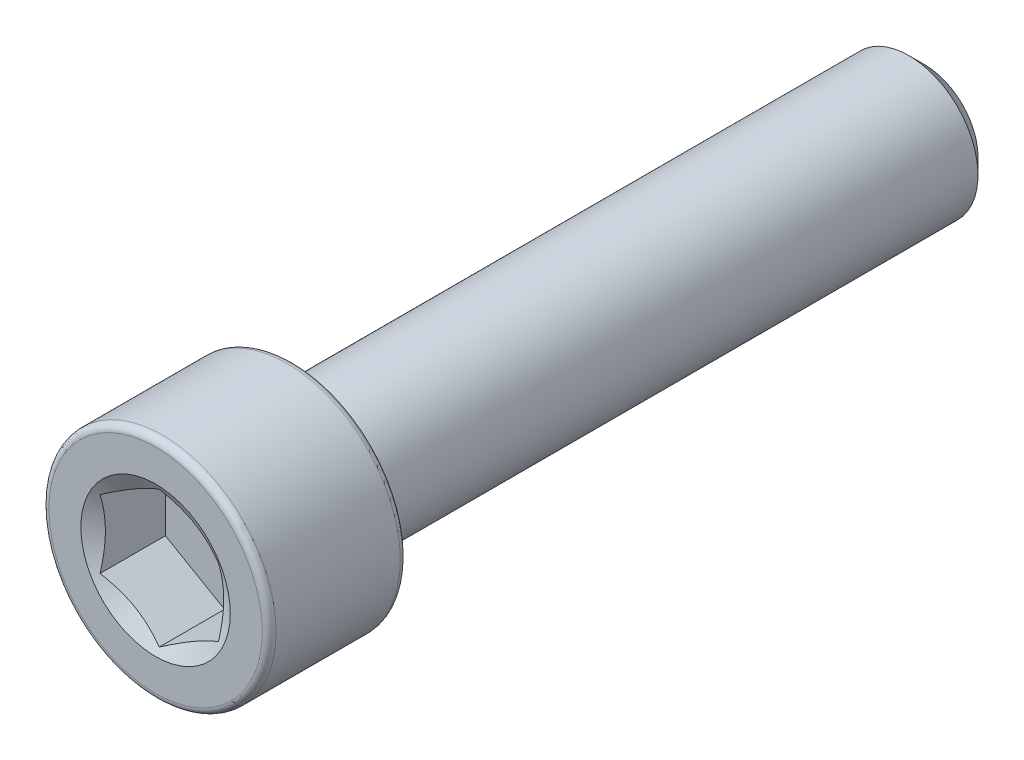
SolidWorks part; units mm, degrees
material "Alloy Steel (SS)"
ref_plane "Front Plane" through (0, 0, 0) normal (0, 0, 1) x (1, 0, 0)
ref_plane "Top Plane" through (0, 0, 0) normal (0, 1, 0) x (1, 0, 0)
ref_plane "Right Plane" through (0, 0, 0) normal (1, 0, 0) x (0, 0, -1)
sketch "Sketch1" plane through (0, 0, 0) normal (1, 0, 0) x (0, 0, -1)
  line L0 (11.6078, 0) -> (-11.6078, 0) construction
  line L1 (-7.4422, 3.429) -> (-7.4422, -3.429) construction
  line L2 (11.6078, 2.0828) -> (11.6078, -2.0828) construction
  line L3 (11.5582, 2.1687) -> (11.9551, 1.4813) construction
  line L4 (11.9055, 1.5672) -> (12.0047, 1.5672) construction
  line L5 (11.9551, 1.4813) -> (12.3519, 2.1687) construction
  line L6 (12.3519, 2.1687) -> (11.5582, 2.1687) construction
  line L7 (11.9551, 1.5672) -> (11.9551, 1.4813) construction
  line L8 (11.9551, 2.1687) -> (11.9551, 2.0828) construction
  line L9 (12.3023, 2.0828) -> (11.6078, 2.0828) construction
  point P4 (-7.4422, 0)
  point P6 (-7.4422, 1.7859)
  point P7 (9.6234, -2.0828)
  point P20 (11.9551, 2.1258)
  dimension "Head Height" = 4.1656
  dimension "Head Diameter" = 6.858
  dimension "Drive Size" = 3.5719
  dimension "Length" = 19.05
  dimension "Screw Size Decimal Equivalent" = 4.1656
  dimension "Pitch" = 0.7937
  dimension "Pitch/8" = 0.0992
  dimension "Thread Note" = 1.9844
sketch "Sketch2" plane through (0, 0, 0) normal (1, 0, 0) x (0, 0, -1)
  line L0 (11.6078, 0) -> (11.6078, 1.6066)
  line L1 (11.6078, 2.0828) -> (11.6078, -2.0828) construction
  line L2 (11.6078, 1.6066) -> (11.1316, 2.0828)
  line L3 (11.1316, 2.0828) -> (-7.4422, 2.0828)
  line L4 (-7.4422, 2.0828) -> (-7.4422, 3.2207)
  line L5 (-7.6505, 3.429) -> (-11.3995, 3.429)
  line L6 (-11.6078, 3.2207) -> (-11.6078, 0)
  line L7 (11.6078, 0) -> (-11.6078, 0) construction
  line L8 (-11.6078, 0) -> (11.6078, 0)
  arc A0 (-7.4422, 3.2207) -> (-7.6505, 3.429) centre (-7.6505, 3.2207) ccw
  arc A1 (-11.3995, 3.429) -> (-11.6078, 3.2207) centre (-11.3995, 3.2207) ccw
  point P19 (-7.4422, 3.429)
  dimension "D3" = 0.2083
  dimension "D1" = 0.4762
  dimension "D2" = 45
revolve "Revolve1" add sketch "Sketch2" angle 360 about L0
sketch "Sketch3" plane through (0, 0, 0) normal (0, 0, 1) x (1, 0, 0)
  line L1 (-1.7859, 1.0311) -> (-1.7859, -1.0311)
  line L2 (-1.7859, -1.0311) -> (0, -2.0622)
  line L3 (0, -2.0622) -> (1.7859, -1.0311)
  line L4 (1.7859, -1.0311) -> (1.7859, 1.0311)
  line L5 (1.7859, 1.0311) -> (0, 2.0622)
  line L6 (0, 2.0622) -> (-1.7859, 1.0311)
  circle A0 centre (0, 0) radius 1.7859 construction
  circle A1 centre (0, 0) radius 3.429 construction
extrude "Cut-Extrude1" cut sketch "Sketch3" against normal blind 2.0828 from vertex starting at point (0, 0, 11.6078)
sketch "Sketch4" plane through (0, 0, 11.6078) normal (0, 0, 1) x (1, 0, 0)
  line L0 (0, 2.0622) -> (0, 2.4484) construction
  line L1 (0, 2.4484) -> (0, 2.8346) construction
  line L2 (0, 2.8346) -> (0, 3.2207) construction
  circle A0 centre (0, 0) radius 2.2553
  point P12 (0, 2.2553)
extrude "Cut-Extrude2" cut sketch "Sketch4" against normal through all draft 60
split "Split1" [suppressed] bodies to split 106 112
sketch "Sketch5" [suppressed] plane through (0, 0, 0) normal (1, 0, 0) x (0, 0, -1)
  line L0 (11.9055, 1.5672) -> (12.0047, 1.5672)
  line L1 (12.0047, 1.5672) -> (12.3271, 2.1258)
  line L2 (12.3271, 2.1258) -> (11.583, 2.1258)
  line L3 (11.583, 2.1258) -> (11.9055, 1.5672)
  line L4 (11.5582, 2.1687) -> (11.9551, 1.4813) construction
sketch "Sketch6" [suppressed] plane through (0, 0, -11.6078) normal (0, 0, -1) x (-1, 0, 0)
  circle A0 centre (0, 0) radius 2.0828
curve "Helix/Spiral1" [suppressed] pitch 0.7937 height 19.8438 turns 25
sweep "Cut-Sweep1" [suppressed] cut profiles "Sketch5" path "Helix/Spiral1"
sketch "Sketch7" [suppressed] plane through (0, 0, 7.4422) normal (0, 0, -1) x (-1, 0, 0)
  circle A0 centre (0, 0) radius 2.1336
  circle A1 centre (0, 0) radius 2.0828 construction
  dimension "D1" = 0.0508
extrude "Boss-Extrude1" [suppressed] add sketch "Sketch7" along normal blind 2.3813 draft 20 and the other way blind 0.4166
ref_plane "Plane1" [suppressed] through (0, 0, 8.8168) normal (0, 0, -1) x (-1, 0, 0)
sketch "Sketch13" [suppressed] plane through (0, 0, 8.8168) normal (0, 0, -1) x (-1, 0, 0)
  line L0 (0.0857, 3.4279) -> (0, 0) construction
  line L1 (0, 0) -> (-0.0857, 3.4279) construction
  line L3 (0.0843, 3.3713) -> (0.0857, 3.4279)
  line L6 (-0.0843, 3.3713) -> (-0.0857, 3.4279)
  arc A1 (0.0857, 3.4279) -> (-0.0857, 3.4279) centre (0, 0) ccw
  circle A2 centre (0, 0) radius 3.429 construction
  arc A3 (0.0843, 3.3713) -> (-0.0843, 3.3713) centre (0, 0) ccw
  point P2 (0, 3.429)
  dimension "D3" = 0.0566
  dimension "D1" = 0.1715
extrude "Cut-Extrude3" [suppressed] cut sketch "Sketch13" against normal blind 2.3244
chamfer "Chamfer3" [suppressed] distance 0.0566 angle 60
chamfer "Chamfer4" [suppressed] distance 0.0566 angle 85
pattern_circular "CirPattern2" [suppressed] count 50 over 360 about axis through (0, 0, -11.6078) along (0, 0, 1) of bodies 134
equation "\"Pitch/8@Sketch1\" = \"Pitch@Sketch1\" / 8"
equation "\"Thread Note@Sketch1\"=\"Pitch@Sketch1\" * 2.5"
equation "\"D1@Sketch2\"=\"Pitch@Sketch1\"*.60"
equation "\"D3@Sketch2\"=\"Head Height@Sketch1\"*.05"
equation "\"D1@Cut-Extrude1\" = \"Head Height@Sketch1\" * .5"
equation "\"D3@Helix/Spiral1\" = \"Length@Sketch1\" + \"Pitch@Sketch1\""
equation "\"D4@Helix/Spiral1\" = \"Pitch@Sketch1\""
equation "\"D2@Boss-Extrude1\" = \"Head Height@Sketch1\" * .1"
equation "\"D1\"= \"Screw Size Decimal Equivalent@Sketch1\" * .4"
equation "\"D1@Plane1\"=\"Head Height@Sketch1\" * .33"
equation "\"D1@Cut-Extrude3\"=( \"Head Height@Sketch1\" - \"D1@Plane1\" - \"D3@Sketch2\" )  * .9"
equation "\"D1@Chamfer3\"=\"D3@Sketch13\""
equation "\"D1@Chamfer4\"=\"D3@Sketch13\""
equation "\"D1@CirPattern2\"=( \"Head Diameter@Sketch1\" * pi )  /  ( 2.5*\"D1@Sketch13\" )"
equation "\"D1@Sketch13\"=\"Head Diameter@Sketch1\" * .025"
equation "\"D3@Sketch13\"=\"D1@Sketch13\"*.33"
equation "\"D1@Boss-Extrude1\"=\"Pitch@Sketch1\"*3"
